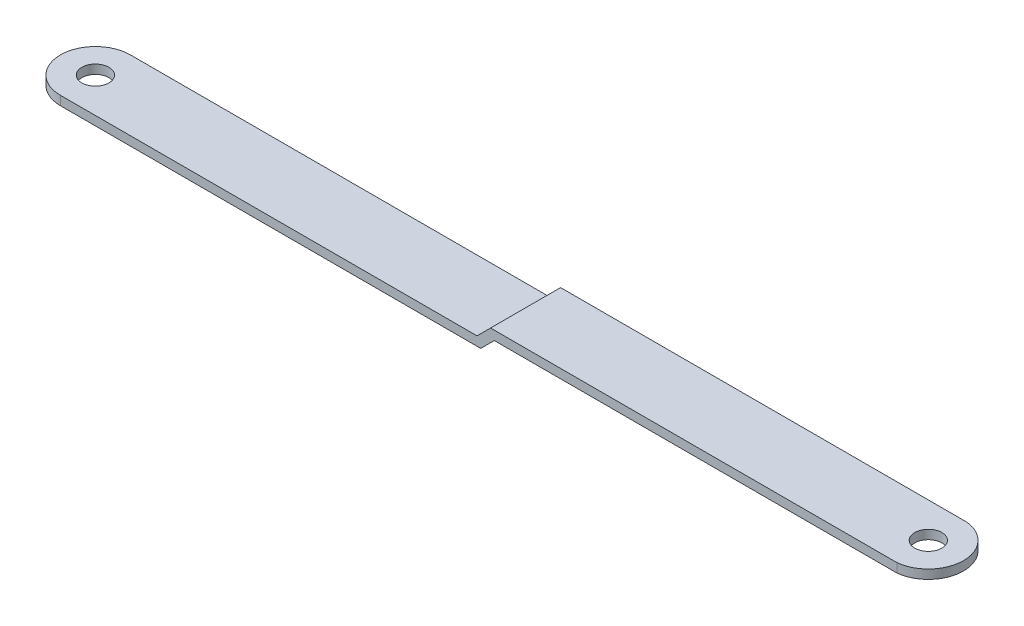
SolidWorks part; units mm, degrees
ref_plane "Спереди" through (0, 0, 0) normal (0, 0, 1) x (1, 0, 0)
ref_plane "Сверху" through (0, 0, 0) normal (0, 1, 0) x (1, 0, 0)
ref_plane "Справа" through (0, 0, 0) normal (1, 0, 0) x (0, 0, -1)
sketch "Эскиз1" plane through (0, 0, 0) normal (0, 0, 1) x (1, 0, 0)
  line L0 (0, 0) -> (100, 0)
  line L1 (100, 0) -> (103, 3)
  line L2 (103, 3) -> (200, 3)
extrude "Вытянуть-Тонкостенный1" add sketch "Эскиз1" along normal blind 15.5 thin thin type one direction wall 2
sketch "Эскиз2" plane through (0, 3, 0) normal (0, 1, 0) x (1, 0, 0)
  line L0 (103, 0) -> (200, 0) construction
  line L1 (103, -15.5) -> (200, -15.5) construction
  line L2 (192.956, 0) -> (7.75, 0)
  line L4 (7.75, -15.5) -> (192.956, -15.5)
  line L5 (0, 0) -> (100, 0) construction
  line L6 (0, -15.5) -> (100, -15.5) construction
  circle A0 centre (192.1834, -7.75) radius 3
  arc A1 (192.956, 0) -> (192.956, -15.5) centre (192.1834, -7.75) cw
  arc A2 (7.75, 0) -> (7.75, -15.5) centre (7.75, -7.75) ccw
  circle A3 centre (7.75, -7.75) radius 3
extrude "Вырез-Вытянуть4" cut sketch "Эскиз2" against normal blind 10 flip side to cut
